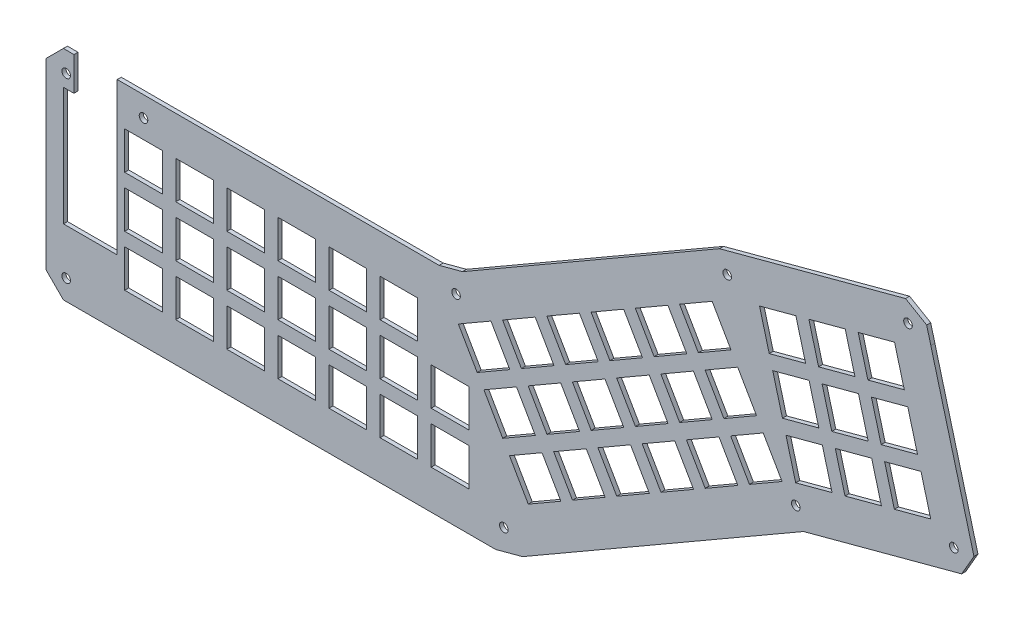
SolidWorks part; units mm, degrees
ref_plane "Plan de face" through (0, 0, 0) normal (0, 0, 1) x (1, 0, 0)
ref_plane "Plan de dessus" through (0, 0, 0) normal (0, 1, 0) x (1, 0, 0)
ref_plane "Plan de droite" through (0, 0, 0) normal (1, 0, 0) x (0, 0, -1)
sketch "Esquisse1" plane through (0, 0, 0) normal (0, 0, 1) x (1, 0, 0)
  line L0 (-73.9886, 18.0851) -> (-59.9886, 18.0851)
  line L1 (-73.9886, 37.0851) -> (-59.9886, 37.0851)
  line L2 (-73.9886, 37.0851) -> (-73.9886, 23.0851)
  line L3 (-73.9886, 23.0851) -> (-59.9886, 23.0851)
  line L4 (-59.9886, 37.0851) -> (-59.9886, 23.0851)
  line L5 (-73.9886, 18.0851) -> (-73.9886, 4.0851)
  line L6 (-73.9886, 4.0851) -> (-59.9886, 4.0851)
  line L7 (-59.9886, 18.0851) -> (-59.9886, 4.0851)
  line L8 (-73.9886, -0.9149) -> (-59.9886, -0.9149)
  line L9 (-73.9886, -0.9149) -> (-73.9886, -14.9149)
  line L10 (-73.9886, -14.9149) -> (-59.9886, -14.9149)
  line L11 (-59.9886, -0.9149) -> (-59.9886, -14.9149)
  line L12 (-73.9886, 37.0851) -> (-73.9886, 18.0851) construction
  line L13 (-54.9886, 18.0851) -> (-40.9886, 18.0851)
  line L14 (-54.9886, 37.0851) -> (-40.9886, 37.0851)
  line L15 (-54.9886, 37.0851) -> (-54.9886, 23.0851)
  line L16 (-54.9886, 23.0851) -> (-40.9886, 23.0851)
  line L17 (-40.9886, 37.0851) -> (-40.9886, 23.0851)
  line L18 (-54.9886, 18.0851) -> (-54.9886, 4.0851)
  line L19 (-54.9886, 4.0851) -> (-40.9886, 4.0851)
  line L20 (-40.9886, 18.0851) -> (-40.9886, 4.0851)
  line L21 (-54.9886, -0.9149) -> (-40.9886, -0.9149)
  line L22 (-54.9886, -0.9149) -> (-54.9886, -14.9149)
  line L23 (-54.9886, -14.9149) -> (-40.9886, -14.9149)
  line L24 (-40.9886, -0.9149) -> (-40.9886, -14.9149)
  line L25 (-54.9886, 37.0851) -> (-54.9886, 18.0851) construction
  line L26 (-35.9886, 18.0851) -> (-21.9886, 18.0851)
  line L27 (-35.9886, 37.0851) -> (-21.9886, 37.0851)
  line L28 (-35.9886, 37.0851) -> (-35.9886, 23.0851)
  line L29 (-35.9886, 23.0851) -> (-21.9886, 23.0851)
  line L30 (-21.9886, 37.0851) -> (-21.9886, 23.0851)
  line L31 (-35.9886, 18.0851) -> (-35.9886, 4.0851)
  line L32 (-35.9886, 4.0851) -> (-21.9886, 4.0851)
  line L33 (-21.9886, 18.0851) -> (-21.9886, 4.0851)
  line L34 (-35.9886, -0.9149) -> (-21.9886, -0.9149)
  line L35 (-35.9886, -0.9149) -> (-35.9886, -14.9149)
  line L36 (-35.9886, -14.9149) -> (-21.9886, -14.9149)
  line L37 (-21.9886, -0.9149) -> (-21.9886, -14.9149)
  line L38 (-35.9886, 37.0851) -> (-35.9886, 18.0851) construction
  line L39 (-16.9886, 18.0851) -> (-2.9886, 18.0851)
  line L40 (-16.9886, 37.0851) -> (-2.9886, 37.0851)
  line L41 (-16.9886, 37.0851) -> (-16.9886, 23.0851)
  line L42 (-16.9886, 23.0851) -> (-2.9886, 23.0851)
  line L43 (-2.9886, 37.0851) -> (-2.9886, 23.0851)
  line L44 (-16.9886, 18.0851) -> (-16.9886, 4.0851)
  line L45 (-16.9886, 4.0851) -> (-2.9886, 4.0851)
  line L46 (-2.9886, 18.0851) -> (-2.9886, 4.0851)
  line L47 (-16.9886, -0.9149) -> (-2.9886, -0.9149)
  line L48 (-16.9886, -0.9149) -> (-16.9886, -14.9149)
  line L49 (-16.9886, -14.9149) -> (-2.9886, -14.9149)
  line L50 (-2.9886, -0.9149) -> (-2.9886, -14.9149)
  line L51 (-16.9886, 37.0851) -> (-16.9886, 18.0851) construction
  line L52 (2.0114, 18.0851) -> (16.0114, 18.0851)
  line L53 (2.0114, 37.0851) -> (16.0114, 37.0851)
  line L54 (2.0114, 37.0851) -> (2.0114, 23.0851)
  line L55 (2.0114, 23.0851) -> (16.0114, 23.0851)
  line L56 (16.0114, 37.0851) -> (16.0114, 23.0851)
  line L57 (2.0114, 18.0851) -> (2.0114, 4.0851)
  line L58 (2.0114, 4.0851) -> (16.0114, 4.0851)
  line L59 (16.0114, 18.0851) -> (16.0114, 4.0851)
  line L60 (2.0114, -0.9149) -> (16.0114, -0.9149)
  line L61 (2.0114, -0.9149) -> (2.0114, -14.9149)
  line L62 (2.0114, -14.9149) -> (16.0114, -14.9149)
  line L63 (16.0114, -0.9149) -> (16.0114, -14.9149)
  line L64 (2.0114, 37.0851) -> (2.0114, 18.0851) construction
  line L65 (21.0114, 18.0851) -> (35.0114, 18.0851)
  line L66 (21.0114, 37.0851) -> (35.0114, 37.0851)
  line L67 (21.0114, 37.0851) -> (21.0114, 23.0851)
  line L68 (21.0114, 23.0851) -> (35.0114, 23.0851)
  line L69 (35.0114, 37.0851) -> (35.0114, 23.0851)
  line L70 (21.0114, 18.0851) -> (21.0114, 4.0851)
  line L71 (21.0114, 4.0851) -> (35.0114, 4.0851)
  line L72 (35.0114, 18.0851) -> (35.0114, 4.0851)
  line L73 (21.0114, -0.9149) -> (35.0114, -0.9149)
  line L74 (21.0114, -0.9149) -> (21.0114, -14.9149)
  line L75 (21.0114, -14.9149) -> (35.0114, -14.9149)
  line L76 (35.0114, -0.9149) -> (35.0114, -14.9149)
  line L77 (21.0114, 37.0851) -> (21.0114, 18.0851) construction
  line L78 (40.0114, 18.0851) -> (54.0114, 18.0851)
  line L79 (40.0114, 37.0851) -> (54.0114, 37.0851) construction
  line L80 (40.0114, 37.0851) -> (40.0114, 23.0851) construction
  line L81 (40.0114, 23.0851) -> (54.0114, 23.0851) construction
  line L82 (54.0114, 37.0851) -> (54.0114, 23.0851) construction
  line L83 (40.0114, 18.0851) -> (40.0114, 4.0851)
  line L84 (40.0114, 4.0851) -> (54.0114, 4.0851)
  line L85 (54.0114, 18.0851) -> (54.0114, 4.0851)
  line L86 (40.0114, -0.9149) -> (54.0114, -0.9149)
  line L87 (40.0114, -0.9149) -> (40.0114, -14.9149)
  line L88 (40.0114, -14.9149) -> (54.0114, -14.9149)
  line L89 (54.0114, -0.9149) -> (54.0114, -14.9149)
  line L90 (40.0114, 37.0851) -> (40.0114, 18.0851) construction
  line L91 (-73.9886, 18.0851) -> (-54.9886, 18.0851) construction
  line L92 (56.0114, 20.0851) -> (56.7532, 18.8002) construction
  line L93 (38.0114, 39.0851) -> (56.0114, 39.0851) construction
  line L94 (56.0114, 39.0851) -> (56.0114, 21.0851) construction
  line L95 (38.0114, 21.0851) -> (56.0114, 21.0851) construction
  line L96 (38.0114, 39.0851) -> (38.0114, 21.0851) construction
  line L97 (19.0114, 39.0851) -> (37.0114, 39.0851) construction
  line L98 (37.0114, 39.0851) -> (37.0114, 21.0851) construction
  line L99 (19.0114, 21.0851) -> (37.0114, 21.0851) construction
  line L100 (19.0114, 39.0851) -> (19.0114, 21.0851) construction
  line L101 (79.4363, 55.512) -> (88.4363, 39.9235) construction
  line L102 (88.4363, 39.9235) -> (72.8478, 30.9235) construction
  line L103 (63.8478, 46.512) -> (72.8478, 30.9235) construction
  line L104 (79.4363, 55.512) -> (63.8478, 46.512) construction
  line L105 (62.9818, 46.012) -> (71.9818, 30.4235) construction
  line L106 (71.9818, 30.4235) -> (56.3933, 21.4235) construction
  line L107 (47.3933, 37.012) -> (56.3933, 21.4235) construction
  line L108 (62.9818, 46.012) -> (47.3933, 37.012) construction
  line L109 (164.2542, 60.603) -> (148.6657, 51.603) construction
  line L110 (62.2497, 43.2799) -> (71.7497, 26.8254) construction
  line L111 (78.7042, 52.7799) -> (88.2042, 36.3254) construction
  line L112 (95.1587, 62.2799) -> (104.6587, 45.8254) construction
  line L113 (111.6132, 71.7799) -> (121.1132, 55.3254) construction
  line L114 (128.0677, 81.2799) -> (137.5677, 64.8254) construction
  line L115 (144.5221, 90.7799) -> (154.0221, 74.3254) construction
  line L116 (148.6657, 51.603) -> (157.6657, 36.0146) construction
  line L117 (69.1254, 3.371) -> (76.1254, -8.7534)
  line L118 (88.2497, -1.7534) -> (76.1254, -8.7534)
  line L119 (81.2497, 10.371) -> (88.2497, -1.7534)
  line L120 (81.2497, 10.371) -> (69.1254, 3.371)
  line L121 (59.6254, 19.8254) -> (66.6254, 7.7011)
  line L122 (78.7497, 14.7011) -> (66.6254, 7.7011)
  line L123 (71.7497, 26.8254) -> (78.7497, 14.7011)
  line L124 (50.1254, 36.2799) -> (57.1254, 24.1556)
  line L125 (69.2497, 31.1556) -> (57.1254, 24.1556)
  line L126 (62.2497, 43.2799) -> (69.2497, 31.1556)
  line L127 (62.2497, 43.2799) -> (50.1254, 36.2799)
  line L128 (71.7497, 26.8254) -> (59.6254, 19.8254)
  line L129 (85.5799, 12.871) -> (92.5799, 0.7466)
  line L130 (104.7042, 7.7466) -> (92.5799, 0.7466)
  line L131 (97.7042, 19.871) -> (104.7042, 7.7466)
  line L132 (97.7042, 19.871) -> (85.5799, 12.871)
  line L133 (76.0799, 29.3254) -> (83.0799, 17.2011)
  line L134 (95.2042, 24.2011) -> (83.0799, 17.2011)
  line L135 (88.2042, 36.3254) -> (95.2042, 24.2011)
  line L136 (66.5799, 45.7799) -> (73.5799, 33.6556)
  line L137 (85.7042, 40.6556) -> (73.5799, 33.6556)
  line L138 (78.7042, 52.7799) -> (85.7042, 40.6556)
  line L139 (78.7042, 52.7799) -> (66.5799, 45.7799)
  line L140 (88.2042, 36.3254) -> (76.0799, 29.3254)
  line L141 (102.0343, 22.371) -> (109.0343, 10.2466)
  line L142 (121.1587, 17.2466) -> (109.0343, 10.2466)
  line L143 (114.1587, 29.371) -> (121.1587, 17.2466)
  line L144 (114.1587, 29.371) -> (102.0343, 22.371)
  line L145 (92.5343, 38.8254) -> (99.5343, 26.7011)
  line L146 (111.6587, 33.7011) -> (99.5343, 26.7011)
  line L147 (104.6587, 45.8254) -> (111.6587, 33.7011)
  line L148 (83.0343, 55.2799) -> (90.0343, 43.1556)
  line L149 (102.1587, 50.1556) -> (90.0343, 43.1556)
  line L150 (95.1587, 62.2799) -> (102.1587, 50.1556)
  line L151 (95.1587, 62.2799) -> (83.0343, 55.2799)
  line L152 (104.6587, 45.8254) -> (92.5343, 38.8254)
  line L153 (118.4888, 31.871) -> (125.4888, 19.7466)
  line L154 (137.6132, 26.7466) -> (125.4888, 19.7466)
  line L155 (130.6132, 38.871) -> (137.6132, 26.7466)
  line L156 (130.6132, 38.871) -> (118.4888, 31.871)
  line L157 (108.9888, 48.3254) -> (115.9888, 36.2011)
  line L158 (128.1132, 43.2011) -> (115.9888, 36.2011)
  line L159 (121.1132, 55.3254) -> (128.1132, 43.2011)
  line L160 (99.4888, 64.7799) -> (106.4888, 52.6556)
  line L161 (118.6132, 59.6556) -> (106.4888, 52.6556)
  line L162 (111.6132, 71.7799) -> (118.6132, 59.6556)
  line L163 (111.6132, 71.7799) -> (99.4888, 64.7799)
  line L164 (121.1132, 55.3254) -> (108.9888, 48.3254)
  line L165 (134.9433, 41.371) -> (141.9433, 29.2466)
  line L166 (154.0677, 36.2466) -> (141.9433, 29.2466)
  line L167 (147.0677, 48.371) -> (154.0677, 36.2466)
  line L168 (147.0677, 48.371) -> (134.9433, 41.371)
  line L169 (125.4433, 57.8254) -> (132.4433, 45.7011)
  line L170 (144.5677, 52.7011) -> (132.4433, 45.7011)
  line L171 (137.5677, 64.8254) -> (144.5677, 52.7011)
  line L172 (115.9433, 74.2799) -> (122.9433, 62.1556)
  line L173 (135.0677, 69.1556) -> (122.9433, 62.1556)
  line L174 (128.0677, 81.2799) -> (135.0677, 69.1556)
  line L175 (128.0677, 81.2799) -> (115.9433, 74.2799)
  line L176 (137.5677, 64.8254) -> (125.4433, 57.8254)
  line L177 (151.3978, 50.871) -> (158.3978, 38.7466)
  line L178 (170.5221, 45.7466) -> (158.3978, 38.7466)
  line L179 (163.5221, 57.871) -> (170.5221, 45.7466)
  line L180 (163.5221, 57.871) -> (151.3978, 50.871)
  line L181 (141.8978, 67.3254) -> (148.8978, 55.2011)
  line L182 (161.0221, 62.2011) -> (148.8978, 55.2011)
  line L183 (154.0221, 74.3254) -> (161.0221, 62.2011)
  line L184 (132.3978, 83.7799) -> (139.3978, 71.6556)
  line L185 (151.5221, 78.6556) -> (139.3978, 71.6556)
  line L186 (144.5221, 90.7799) -> (151.5221, 78.6556)
  line L187 (144.5221, 90.7799) -> (132.3978, 83.7799)
  line L188 (154.0221, 74.3254) -> (141.8978, 67.3254)
  line L189 (173.2542, 45.0146) -> (157.6657, 36.0146) construction
  line L190 (164.2542, 60.603) -> (173.2542, 45.0146) construction
  line L191 (178.3169, 34.0986) -> (169.0534, 56.4627) construction
  line L192 (169.5193, 62.7839) -> (174.1781, 45.3972) construction
  line L193 (174.1781, 45.3972) -> (191.5647, 50.056) construction
  line L194 (186.906, 67.4426) -> (191.5647, 50.056) construction
  line L195 (162.1337, 98.0749) -> (167.0513, 79.7223) construction
  line L196 (169.5193, 62.7839) -> (186.906, 67.4426) construction
  line L197 (167.0513, 79.7223) -> (180.5742, 83.3457)
  line L198 (162.1337, 98.0749) -> (175.6567, 101.6983)
  line L199 (162.1337, 98.0749) -> (165.7572, 84.5519)
  line L200 (165.7572, 84.5519) -> (179.2801, 88.1754)
  line L201 (175.6567, 101.6983) -> (179.2801, 88.1754)
  line L202 (167.0513, 79.7223) -> (170.6747, 66.1993)
  line L203 (170.6747, 66.1993) -> (184.1977, 69.8228)
  line L204 (180.5742, 83.3457) -> (184.1977, 69.8228)
  line L205 (171.9688, 61.3697) -> (185.4918, 64.9932)
  line L206 (171.9688, 61.3697) -> (175.5923, 47.8467)
  line L207 (175.5923, 47.8467) -> (189.1152, 51.4702)
  line L208 (185.4918, 64.9932) -> (189.1152, 51.4702)
  line L209 (185.4038, 84.6398) -> (198.9268, 88.2633)
  line L210 (180.4863, 102.9924) -> (194.0092, 106.6159)
  line L211 (180.4863, 102.9924) -> (184.1097, 89.4695)
  line L212 (184.1097, 89.4695) -> (197.6327, 93.0929)
  line L213 (194.0092, 106.6159) -> (197.6327, 93.0929)
  line L214 (185.4038, 84.6398) -> (189.0273, 71.1169)
  line L215 (189.0273, 71.1169) -> (202.5503, 74.7403)
  line L216 (198.9268, 88.2633) -> (202.5503, 74.7403)
  line L217 (190.3214, 66.2873) -> (203.8444, 69.9107)
  line L218 (190.3214, 66.2873) -> (193.9449, 52.7643)
  line L219 (193.9449, 52.7643) -> (207.4678, 56.3878)
  line L220 (203.8444, 69.9107) -> (207.4678, 56.3878)
  line L221 (187.8719, 67.7015) -> (192.5307, 50.3148) construction
  line L222 (192.5307, 50.3148) -> (209.9173, 54.9735) construction
  line L223 (205.2586, 72.3602) -> (209.9173, 54.9735) construction
  line L224 (180.4863, 102.9924) -> (185.4038, 84.6398) construction
  line L225 (187.8719, 67.7015) -> (205.2586, 72.3602) construction
  line L226 (203.7564, 89.5574) -> (217.2794, 93.1809)
  line L227 (198.8389, 107.91) -> (212.3618, 111.5335)
  line L228 (198.8389, 107.91) -> (202.4623, 94.387)
  line L229 (202.4623, 94.387) -> (215.9853, 98.0105)
  line L230 (212.3618, 111.5335) -> (215.9853, 98.0105)
  line L231 (203.7564, 89.5574) -> (207.3799, 76.0344)
  line L232 (207.3799, 76.0344) -> (220.9029, 79.6579)
  line L233 (217.2794, 93.1809) -> (220.9029, 79.6579)
  line L234 (208.674, 71.2048) -> (222.197, 74.8283)
  line L235 (208.674, 71.2048) -> (212.2975, 57.6819)
  line L236 (212.2975, 57.6819) -> (225.8204, 61.3053)
  line L237 (222.197, 74.8283) -> (225.8204, 61.3053)
  line L238 (206.2245, 72.619) -> (210.8833, 55.2324) construction
  line L239 (210.8833, 55.2324) -> (228.2699, 59.8911) construction
  line L240 (223.6112, 77.2778) -> (228.2699, 59.8911) construction
  line L241 (198.8389, 107.91) -> (203.7564, 89.5574) construction
  line L242 (206.2245, 72.619) -> (223.6112, 77.2778) construction
  line L243 (167.0513, 79.7223) -> (185.4038, 84.6398) construction
  line L244 (38.0114, 20.0851) -> (56.0114, 20.0851) construction
  line L245 (56.0114, 20.0851) -> (56.0114, 2.0851) construction
  line L246 (38.0114, 2.0851) -> (56.0114, 2.0851) construction
  line L247 (38.0114, 20.0851) -> (38.0114, 2.0851) construction
  line L248 (72.4818, 29.5575) -> (56.8933, 20.5575) construction
  line L249 (56.8933, 20.5575) -> (65.8933, 4.969) construction
  line L250 (81.4818, 13.969) -> (65.8933, 4.969) construction
  line L251 (72.4818, 29.5575) -> (81.4818, 13.969) construction
  line L252 (56.8933, 20.5575) -> (57.6111, 19.3142) construction
  line L253 (164.6018, 81.1365) -> (169.2605, 63.7498) construction
  line L254 (169.2605, 63.7498) -> (186.6472, 68.4086) construction
  line L255 (181.9884, 85.7952) -> (186.6472, 68.4086) construction
  line L256 (164.6018, 81.1365) -> (181.9884, 85.7952) construction
  line L257 (154.7542, 77.0575) -> (163.7542, 61.469) construction
  line L258 (163.7542, 61.469) -> (148.1657, 52.469) construction
  line L259 (139.1657, 68.0575) -> (148.1657, 52.469) construction
  line L260 (154.7542, 77.0575) -> (139.1657, 68.0575) construction
  line L261 (196.3894, 109.3242) -> (213.776, 113.983) construction
  line L262 (-94.7538, 35.7952) -> (-76.7538, 35.7952) construction
  line L263 (-94.7538, 35.7952) -> (-94.7538, 2.7952) construction
  line L264 (-94.7538, 2.7952) -> (-76.7538, 2.7952) construction
  line L265 (-76.7538, 35.7952) -> (-76.7538, 2.7952) construction
  line L266 (213.776, 113.983) -> (218.4348, 96.5963) construction
  line L267 (201.0481, 91.9375) -> (218.4348, 96.5963) construction
  line L268 (196.3894, 109.3242) -> (201.0481, 91.9375) construction
  line L269 (-75.9886, -16.9149) -> (-57.9886, -16.9149) construction
  line L270 (-57.9886, 1.0851) -> (-57.9886, -16.9149) construction
  line L271 (-75.9886, 1.0851) -> (-57.9886, 1.0851) construction
  line L272 (-75.9886, 1.0851) -> (-75.9886, -16.9149) construction
  line L273 (38.0114, -16.9149) -> (56.0114, -16.9149) construction
  line L274 (56.0114, 1.0851) -> (56.0114, -16.9149) construction
  line L275 (38.0114, 1.0851) -> (56.0114, 1.0851) construction
  line L276 (38.0114, 1.0851) -> (38.0114, -16.9149) construction
  line L277 (-75.9886, 39.0851) -> (-57.9886, 39.0851) construction
  line L278 (-57.9886, 39.0851) -> (-57.9886, 21.0851) construction
  line L279 (-75.9886, 21.0851) -> (-57.9886, 21.0851) construction
  line L280 (-75.9886, 39.0851) -> (-75.9886, 21.0851) construction
  line L281 (145.2542, 93.512) -> (129.6657, 84.512) construction
  line L282 (129.6657, 84.512) -> (138.6657, 68.9235) construction
  line L283 (154.2542, 77.9235) -> (138.6657, 68.9235) construction
  line L284 (145.2542, 93.512) -> (154.2542, 77.9235) construction
  line L285 (223.4353, 116.5711) -> (228.0941, 99.1845) construction
  line L286 (148.2159, 106.7689) -> (211.1879, 123.6422) construction
  line L287 (177.5508, 35.9482) -> (235.6877, 51.5259) construction
  line L288 (177.5508, 35.9482) -> (72.9989, -24.4149) construction
  line L289 (-95.7538, -26.9149) -> (63.6687, -26.9149) construction
  line L290 (-100.7538, 35.7952) -> (-100.7538, -21.9149) construction
  line L291 (-75.9886, 49.0851) -> (43.3046, 49.0851) construction
  line L292 (148.2159, 106.7689) -> (52.6347, 51.5851) construction
  line L293 (-75.9886, 49.0851) -> (-57.9886, 49.0851) construction
  line L294 (140.2542, 102.1722) -> (124.6657, 93.1722) construction
  line L295 (193.8012, 118.9835) -> (211.1879, 123.6422) construction
  line L296 (213.4714, 45.5731) -> (230.8581, 50.2318) construction
  line L297 (38.0114, -26.9149) -> (38.0114, -85.4624) construction
  line L298 (178.2542, 36.3543) -> (162.6657, 27.3543) construction
  line L299 (38.0114, -26.9149) -> (56.0114, -26.9149) construction
  line L300 (-100.7538, 2.7952) -> (-100.7538, -38.0419) construction
  line L301 (-100.7538, 35.7952) -> (-100.7538, 2.7952) construction
  line L302 (-75.9886, 49.0851) -> (-95.7538, 49.0851) construction
  line L303 (-100.7538, 44.0851) -> (-100.7538, 35.7952) construction
  line L304 (211.1879, 123.6422) -> (216.0732, 124.9512) construction
  line L305 (222.1691, 121.4083) -> (223.4353, 116.5711) construction
  line L306 (228.0941, 99.1845) -> (239.2233, 57.6497) construction
  line L307 (216.0732, 124.9512) -> (222.1691, 121.4083) construction
  line L308 (235.6877, 51.5259) -> (239.2233, 57.6497) construction
  line L309 (63.6687, -26.9149) -> (72.9989, -24.4149) construction
  line L310 (52.6347, 51.5851) -> (43.3046, 49.0851) construction
  line L311 (-95.7538, 49.0851) -> (-100.7538, 44.0851) construction
  line L312 (-100.7538, -21.9149) -> (-95.7538, -26.9149) construction
  line L313 (-95.7538, 49.0851) -> (-95.7538, 44.0851) construction
  line L314 (-95.7538, 44.0851) -> (-100.7538, 44.0851) construction
  line L315 (-95.7538, -26.9149) -> (-95.7538, -21.9149) construction
  line L316 (68.3338, -25.6649) -> (67.0397, -20.8353) construction
  line L317 (47.9697, 50.3351) -> (49.2637, 45.5055) construction
  line L318 (177.5508, 35.9482) -> (175.6374, 40.5676) construction
  line L319 (148.2159, 106.7689) -> (150.1293, 102.1495) construction
  line L320 (239.2233, 57.6497) -> (234.3936, 56.3556) construction
  line L321 (216.0732, 124.9512) -> (217.3634, 120.1206) construction
  line L322 (-66.9886, 37.0851) -> (-66.9886, 49.0851) construction
  line L323 (-76.7538, 35.7952) -> (-96.7538, 35.7952) construction
  line L324 (-95.7538, 44.0851) -> (-65.1374, 44.0851) construction
  line L325 (-76.7538, 39.0851) -> (-76.7586, 39.0851)
  line L326 (-76.7538, 39.0851) -> (-76.7538, -4.9149)
  line L327 (-76.7538, 1.0851) -> (-96.7538, 1.0851) construction
  line L328 (-96.7538, 39.0851) -> (-96.7538, -4.9149)
  line L329 (-75.9886, 50.5851) -> (43.1071, 50.5851) construction
  line L330 (52.0557, 52.9829) -> (43.1071, 50.5851) construction
  line L331 (147.6369, 108.1667) -> (52.0557, 52.9829) construction
  line L332 (147.6369, 108.1667) -> (210.7996, 125.0911) construction
  line L333 (210.7996, 125.0911) -> (216.2876, 126.5616) construction
  line L334 (216.2876, 126.5616) -> (223.4622, 122.3917) construction
  line L335 (223.4622, 122.3917) -> (224.8853, 116.9552) construction
  line L336 (224.8853, 116.9552) -> (229.5429, 99.5727) construction
  line L337 (229.5429, 99.5727) -> (240.833, 57.4377) construction
  line L338 (236.6761, 50.2379) -> (240.833, 57.4377) construction
  line L339 (178.1298, 34.5504) -> (236.6761, 50.2379) construction
  line L340 (178.1298, 34.5504) -> (73.5778, -25.8127) construction
  line L341 (63.8662, -28.4149) -> (73.5778, -25.8127) construction
  line L342 (-96.3751, -28.4149) -> (63.8662, -28.4149) construction
  line L343 (-102.2538, -22.5362) -> (-96.3751, -28.4149) construction
  line L344 (-102.2538, 35.7952) -> (-102.2538, -22.5362) construction
  line L345 (-102.2538, 44.7064) -> (-102.2538, 35.7952) construction
  line L346 (-96.3751, 50.5851) -> (-102.2538, 44.7064) construction
  line L347 (-75.9886, 50.5851) -> (-96.3751, 50.5851) construction
  line L348 (-75.9886, 52.5851) -> (42.8438, 52.5851) construction
  line L349 (51.2838, 54.8466) -> (42.8438, 52.5851) construction
  line L350 (146.8649, 110.0304) -> (51.2838, 54.8466) construction
  line L351 (146.8649, 110.0304) -> (210.282, 127.023) construction
  line L352 (210.282, 127.023) -> (216.5734, 128.7087) construction
  line L353 (216.5734, 128.7087) -> (225.1863, 123.7029) construction
  line L354 (225.1863, 123.7029) -> (226.8187, 117.4673) construction
  line L355 (226.8187, 117.4673) -> (231.4748, 100.0903) construction
  line L356 (231.4748, 100.0903) -> (242.9792, 57.1552) construction
  line L357 (237.994, 48.5204) -> (242.9792, 57.1552) construction
  line L358 (178.9017, 32.6867) -> (237.994, 48.5204) construction
  line L359 (178.9017, 32.6867) -> (74.3498, -27.6764) construction
  line L360 (64.1295, -30.4149) -> (74.3498, -27.6764) construction
  line L361 (-97.2035, -30.4149) -> (64.1295, -30.4149) construction
  line L362 (-104.2538, -23.3646) -> (-97.2035, -30.4149) construction
  line L363 (-104.2538, 35.7952) -> (-104.2538, -23.3646) construction
  line L364 (-104.2538, 45.5349) -> (-104.2538, 35.7952) construction
  line L365 (-97.2035, 52.5851) -> (-104.2538, 45.5349) construction
  line L366 (-75.9886, 52.5851) -> (-97.2035, 52.5851) construction
  line L367 (-75.9886, 51.5851) -> (42.9755, 51.5851)
  line L368 (51.6698, 53.9147) -> (42.9755, 51.5851)
  line L369 (147.2509, 109.0986) -> (51.6698, 53.9147)
  line L370 (147.2509, 109.0986) -> (210.5408, 126.057)
  line L371 (210.5408, 126.057) -> (216.4305, 127.6352)
  line L372 (216.4305, 127.6352) -> (224.3243, 123.0473)
  line L373 (224.3243, 123.0473) -> (225.852, 117.2112)
  line L374 (225.852, 117.2112) -> (230.5089, 99.8315)
  line L375 (230.5089, 99.8315) -> (241.9061, 57.2965)
  line L376 (237.335, 49.3791) -> (241.9061, 57.2965)
  line L377 (178.5158, 33.6186) -> (237.335, 49.3791)
  line L378 (178.5158, 33.6186) -> (73.9638, -26.7445)
  line L379 (63.9979, -29.4149) -> (73.9638, -26.7445)
  line L380 (-96.7893, -29.4149) -> (63.9979, -29.4149)
  line L381 (-103.2538, -22.9504) -> (-96.7893, -29.4149)
  line L382 (-103.2538, 35.7952) -> (-103.2538, -22.9504)
  line L383 (-103.2538, 45.1206) -> (-103.2538, 35.7952)
  line L384 (-96.7893, 51.5851) -> (-103.2538, 45.1206)
  line L385 (-75.9886, 51.5851) -> (-76.7586, 51.5851)
  line L386 (-86.7538, 39.0851) -> (-86.7538, 51.5851) construction
  line L389 (-92.8638, 51.5851) -> (-96.7893, 51.5851)
  line L390 (-92.8638, 39.0851) -> (-96.7538, 39.0851)
  line L391 (-75.9886, 51.5851) -> (-96.7893, 51.5851) construction
  line L392 (-76.7538, -4.9149) -> (-96.7538, -4.9149)
  line L393 (-92.8638, 51.5851) -> (-92.8638, 39.0851)
  line L394 (-76.7586, 51.5851) -> (-76.7586, 39.0851)
  circle A0 centre (-95.7538, 44.0851) radius 1.5 construction
  circle A1 centre (-95.7538, -21.9149) radius 1.5 construction
  circle A2 centre (67.0397, -20.8353) radius 1.5 construction
  circle A3 centre (49.2637, 45.5055) radius 1.5 construction
  circle A4 centre (175.6374, 40.5676) radius 1.5 construction
  circle A5 centre (150.1293, 102.1495) radius 1.5 construction
  circle A6 centre (234.3936, 56.3556) radius 1.5 construction
  circle A7 centre (217.3634, 120.1206) radius 1.5 construction
  circle A8 centre (-66.9886, 44.0851) radius 1.5 construction
  circle A9 centre (-95.7538, 44.0851) radius 1.6
  circle A10 centre (-66.9886, 44.0851) radius 1.6
  circle A11 centre (-95.7538, -21.9149) radius 1.6
  circle A12 centre (67.0397, -20.8353) radius 1.6
  circle A13 centre (49.2637, 45.5055) radius 1.6
  circle A14 centre (175.6374, 40.5676) radius 1.6
  circle A15 centre (150.1293, 102.1495) radius 1.6
  circle A16 centre (217.3634, 120.1206) radius 1.6
  circle A17 centre (234.3936, 56.3556) radius 1.6
  point P304 (48.3046, 49.0851)
  point P305 (240.5174, 52.82)
  point P308 (68.6687, -26.9149)
  point P309 (-100.7538, -26.9149)
  point P311 (-100.7538, 49.0851)
  point P312 (220.9029, 126.2453)
  point P430 (-86.7538, 45.3351)
  dimension "D32" = 3
  dimension "D33" = 5
  dimension "D40" = 5
  dimension "D41" = 5
  dimension "D42" = 5
  dimension "D43" = 5
  dimension "D44" = 20
  dimension "D45" = 1.5
  dimension "D49" = 0.1
  dimension "D1" = 14
  dimension "D2" = 14
  dimension "D4" = 19
  dimension "D6" = 19
  dimension "D7" = 30
  dimension "D10" = 1
  dimension "D11" = 2
  dimension "D13" = 0.5
  dimension "D15" = 2
  dimension "D12" = 7.5
  dimension "D14" = 19
  dimension "D18" = 2
  dimension "D20" = 18
  dimension "D21" = 33
  dimension "D22" = 2
  dimension "D51" = 2.89
  dimension "D52" = 9.77
  dimension "D8" = 2
  dimension "D9" = 2
  dimension "D16" = 2
  dimension "D19" = 2
  dimension "D23" = 2
  dimension "D24" = 10
  dimension "D25" = 10
  dimension "D26" = 10
  dimension "D27" = 10
  dimension "D28" = 10
  dimension "D29" = 6
  dimension "D30" = 10
  dimension "D31" = 10
  dimension "D46" = 2
  dimension "D47" = 1
  dimension "D48" = 0.1
  dimension "D50" = 6
  dimension "D3" = 3
  dimension "D5" = 7
  dimension "D17" = 3
extrude "Boss.-Extru.1" add sketch "Esquisse1" along normal blind 1.5
